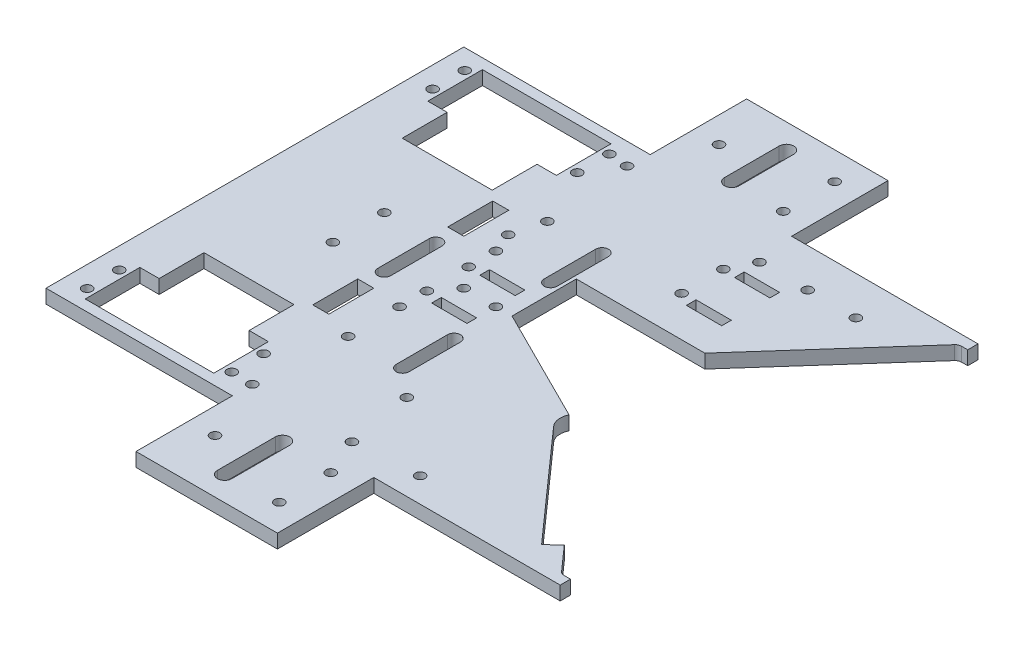
SolidWorks part; units mm, degrees
material "Acrylic (Medium-high impact)"
ref_plane "Front Plane" through (0, 0, 0) normal (0, 0, 1) x (1, 0, 0)
ref_plane "Top Plane" through (0, 0, 0) normal (0, 1, 0) x (1, 0, 0)
ref_plane "Right Plane" through (0, 0, 0) normal (1, 0, 0) x (0, 0, -1)
sketch "Sketch2" plane through (0, 0, 0) normal (0, 1, 0) x (1, 0, 0)
  line L2 (0, 0) -> (0, 65)
  line L3 (0, 65) -> (58, 65)
  line L4 (160, 0) -> (160, 65)
  line L8 (0, 0) -> (160, 0)
  line L9 (102, 65) -> (160, 65)
  line L11 (102, 65) -> (102, 95)
  line L12 (58, 65) -> (58, 95)
  line L13 (58, 95) -> (102, 95)
  dimension "D1" = 65
  dimension "D2" = 160
  dimension "D3" = 44
  dimension "D4" = 30
extrude "Boss-Extrude1" add sketch "Sketch2" along normal blind 4.3
mirror "Mirror1" about plane through (0, 4.3, 0) normal (0, 0, -1) of bodies 101
sketch "Sketch3" plane through (0, 4.3, 0) normal (0, 1, 0) x (1, 0, 0)
  line L0 (160, 61.8) -> (160, -61.8)
  line L1 (120.0126, 20) -> (157.1565, 61.8)
  line L3 (80.0126, 0) -> (80.0126, 20)
  line L4 (80.0126, 20) -> (120.0126, 20)
  line L12 (160, 65) -> (102, 65)
  line L13 (102, 65) -> (102, 95)
  line L15 (102, 95) -> (58, 95)
  line L16 (58, 65) -> (0, 65)
  line L17 (0, 65) -> (0, -65)
  line L18 (0, -65) -> (58, -65)
  line L20 (58, 95) -> (58, 65)
  line L22 (102, -65) -> (160, -65)
  line L23 (160, -65) -> (160, 65)
  line L36 (58, -65) -> (58, -95)
  line L38 (58, -95) -> (102, -95)
  line L39 (58, -95) -> (102, -95)
  line L40 (102, -95) -> (102, -65)
  line L42 (160, -61.8) -> (157.1556, -61.8)
  line L45 (160, 61.8) -> (157.1565, 61.8)
  line L48 (80.0126, 0) -> (120, -20)
  line L49 (120, -20) -> (157.1556, -61.8)
  line M24 (160, -65) -> (160, 65)
  dimension "D2" = 130
  dimension "D3" = 20
  dimension "D4" = 40
  dimension "D1" = 0
extrude "Cut-Extrude1" cut sketch "Sketch3" against normal blind 4.5 contours L48 L49 L1 L4 L3 M24 region at (132.7054, 4.3, -1.1594)
fillet "Fillet1" radius 2 2 edges at (157.1565, 2.15, -61.8) (157.1556, 2.15, 61.8)
ref_axis "Axis1" through (80, 4.3, 95) along (0, 0, -1)
sketch "Sketch4" plane through (0, 4.3, 0) normal (0, 1, 0) x (1, 0, 0)
  line L0 (80, -95) -> (80, 95)
  line L1 (102, -95) -> (58, -95) construction
  line L2 (102, 95) -> (58, 95) construction
ref_plane "Plane2" through (0, 4.3, 0) normal (0, 1, 0) x (1, 0, 0)
sketch "Sketch6" plane through (0, 4.3, 0) normal (0, 1, 0) x (1, 0, 0)
  line L3 (9, -61.8) -> (49, -61.8)
  line L6 (29, -45.8) -> (29, -44.8)
  line L7 (9, -44.8) -> (15, -44.8)
  line L11 (43, -44.8) -> (43, -30.8418)
  line L12 (15, -44.8) -> (15, -30.8418)
  line L13 (15, -30.8418) -> (43, -30.8418)
  line L15 (0, 0) -> (80.0126, 0)
  line L16 (80.0126, 0) -> (120, -20) construction
  line L18 (9, 44.8) -> (15, 44.8)
  line L20 (15, 30.8418) -> (43, 30.8418)
  line L21 (15, 44.8) -> (15, 30.8418)
  line L22 (43, 44.8) -> (43, 30.8418)
  line L25 (15, -45.8) -> (15, -30.8418) construction
  line L27 (9, 61.8) -> (49, 61.8)
  line L30 (4, -61.8) -> (3, -61.8)
  line L31 (0, -61.8) -> (160, -61.8) construction
  line L32 (3, -61.8) -> (4, -61.8)
  line L33 (3, -44.8) -> (3, -62.8) construction
  line L34 (3, -62.8) -> (55, -62.8) construction
  line L35 (55, -44.8) -> (55, -62.8) construction
  line L36 (4, -61.8) -> (54, -61.8) construction
  line L37 (0, 61.8) -> (160, 61.8) construction
  line L38 (54, 61.8) -> (55, 61.8)
  line L39 (54, 61.8) -> (55, 61.8)
  line L40 (43, 44.8) -> (49, 44.8)
  line L41 (4, -45.8) -> (4, -61.8) construction
  line L42 (4, -45.8) -> (54, -45.8) construction
  line L43 (43, -44.8) -> (49, -44.8)
  line L44 (3, -44.8) -> (55, -44.8) construction
  line L45 (29, -45.8) -> (29, -30.8418) construction
  line L46 (43, -45.8) -> (43, -30.8418) construction
  line L47 (54, -45.8) -> (54, -61.8) construction
  line L48 (9, -61.8) -> (49, -61.8)
  line L52 (9, 61.8) -> (9, 44.8)
  line L53 (55, 61.8) -> (54, 61.8)
  line L56 (49, 61.8) -> (49, 44.8)
  line L59 (3, -61.8) -> (4, -61.8)
  line L60 (9, -44.8) -> (9, -61.8)
  line L64 (49, -44.8) -> (49, -61.8)
  dimension "D4" = 1
  dimension "D5" = 14
  dimension "D6" = 14
extrude "Cut-Extrude2" cut sketch "Sketch6" against normal blind 10
sketch "Sketch8" plane through (0, 4.3, 0) normal (0, 1, 0) x (1, 0, 0)
  circle A0 centre (6.5, 58.8) radius 1.5
  circle A1 centre (6.5, 48.8) radius 1.5
  circle A2 centre (51.5, 48.8) radius 1.5
  circle A3 centre (51.5, 58.8) radius 1.5
  circle A4 centre (6.5, -48.7) radius 1.5
  circle A5 centre (6.5, -58.7) radius 1.5
  circle A6 centre (51.5, -58.7) radius 1.5
  circle A7 centre (51.5, -48.8) radius 1.5
  point P23 (0, 0)
  dimension "D7" = 3
extrude "Cut-Extrude3" cut sketch "Sketch8" against normal blind 10
sketch "Sketch9" plane through (0, 0, 0) normal (0, -1, 0) x (1, 0, 0)
  line L0 (75.75, 69.4) -> (75.75, 87.4)
  line L1 (75.75, -87.4) -> (75.75, -70.4)
  line L2 (80.25, -87.4) -> (80.25, -70.4)
  line L4 (80.25, 69.4) -> (80.25, 87.4)
  circle A0 centre (94, 70.4) radius 1.5
  circle A1 centre (66, 78.4) radius 1.5
  circle A2 centre (66, -78.4) radius 1.5
  circle A3 centre (94, -86.4) radius 1.5
  circle A4 centre (94, 86.4) radius 1.5
  circle A5 centre (94, -70.4) radius 1.5
  arc A6 (75.75, -87.4) -> (80.25, -87.4) centre (78, -87.4) ccw
  arc A7 (80.25, -70.4) -> (75.75, -70.4) centre (78, -70.4) ccw
  arc A10 (75.75, 69.4) -> (80.25, 69.4) centre (78, 69.4) ccw
  arc A12 (80.25, 87.4) -> (75.75, 87.4) centre (78, 87.4) ccw
  dimension "D1" = 3
extrude "Cut-Extrude4" cut sketch "Sketch9" against normal blind 10
sketch "Sketch7" plane through (0, 4.3, 0) normal (0, 1, 0) x (1, 0, 0)
  line L0 (0, 0) -> (80.0126, 0)
  line L1 (0, 65) -> (0, -65) construction
  line L2 (80.0126, 0) -> (80.0126, 20) construction
  line L3 (80, -95) -> (80, 95) construction
  line L4 (64, -9) -> (75, -9)
  line L5 (64, -6) -> (75, -6)
  line L6 (64, -9) -> (64, -6)
  line L7 (75, -9) -> (75, -6)
  line L8 (64, -7.5) -> (75, -7.5)
  line L9 (64, 7.5) -> (75, 7.5)
  line L10 (75, 9) -> (75, 6)
  line L11 (64, 9) -> (64, 6)
  line L12 (64, 6) -> (75, 6)
  line L13 (64, 9) -> (75, 9)
  line L14 (104.2547, 30) -> (115.2547, 30)
  line L15 (104.2547, 33) -> (115.2547, 33)
  line L16 (104.2547, 30) -> (104.2547, 33)
  line L17 (115.2547, 30) -> (115.2547, 33)
  line L20 (115.2547, 48) -> (115.2547, 45)
  line L21 (104.2547, 48) -> (104.2547, 45)
  line L22 (104.2547, 45) -> (115.2547, 45)
  line L23 (104.2547, 48) -> (115.2547, 48)
  line L24 (80.0126, 20) -> (120.0126, 20) construction
  circle A0 centre (60.0126, -6.5) radius 1.5
  circle A1 centre (60.0126, 6.5) radius 1.5
  circle A2 centre (100.2673, 32.5) radius 1.5
  circle A3 centre (100.2673, 45.5) radius 1.5
  dimension "D1" = 3
  dimension "D8" = 3
  dimension "D2" = 6.5
  dimension "D3" = 20
  dimension "D6" = 11
  dimension "D4" = 5
  dimension "D5" = 3
  dimension "D7" = 7.5
  dimension "D9" = 11
  dimension "D10" = 3
  dimension "D11" = 12
  dimension "D12" = 13
  dimension "D13" = 10
  dimension "D14" = 3.9874
  dimension "D15" = 0.5
  dimension "D16" = 0.5
  dimension "D17" = 3.9874
sketch "Sketch10" plane through (0, 4.3, 0) normal (0, 1, 0) x (1, 0, 0)
  line L0 (120, -20) -> (156.5589, -61.1287) construction
  line L1 (123.3218, -23.737) -> (149.8964, -53.6334)
  line L2 (116.263, -23.3218) -> (146.1593, -56.9552)
  line L3 (149.8964, -53.6334) -> (146.1593, -56.9552)
  line L4 (120, -20) -> (156.5589, -61.1287) construction
  line L5 (116.263, -23.3218) -> (152.8218, -64.4505) construction
  arc A0 (123.3218, -23.737) -> (116.263, -23.3218) centre (120, -20) ccw
  dimension "D1" = 5
  dimension "D2" = 45
extrude "Cut-Extrude5" cut sketch "Sketch10" against normal blind 10
sketch "Sketch11" plane through (0, 0, 0) normal (0, -1, 0) x (1, 0, 0)
  line L0 (0, 0) -> (80.0126, 0) construction
  line L1 (80, 95) -> (80, -95) construction
  line L2 (80.0126, 0) -> (0, 0)
  line L4 (75, 31.0313) -> (75, 15.0313)
  line L6 (79, 31.0313) -> (79, 15.0313)
  line L7 (79, -31.0313) -> (79, -15.0313)
  line L8 (75, -31.0313) -> (75, -15.0313)
  circle A0 centre (60, 31) radius 1.5
  circle A1 centre (60, 15) radius 1.5
  arc A2 (75, 31.0313) -> (79, 31.0313) centre (77, 31.0313) cw
  arc A3 (75, 15.0313) -> (79, 15.0313) centre (77, 15.0313) ccw
  arc A4 (75, -15.0313) -> (79, -15.0313) centre (77, -15.0313) cw
  arc A5 (75, -31.0313) -> (79, -31.0313) centre (77, -31.0313) ccw
  circle A6 centre (60, -15) radius 1.5
  circle A7 centre (60, -31) radius 1.5
  dimension "D1" = 3
  dimension "D2" = 16
  dimension "D3" = 15
  dimension "D4" = 20
  dimension "D5" = 15
  dimension "D6" = 4
extrude "Cut-Extrude6" cut sketch "Sketch11" against normal blind 10 contours L4 A3 L6 A2 | L8 A5 L7 A4 | A7 | A0 | A1 | A6 region at (77, 0, 23.0313) region at (77, 0, -23.0313) region at (60, 0, -31)
sketch "Sketch12" plane through (0, 0, 0) normal (0, -1, 0) x (-1, 0, 0)
  line L0 (0, 0) -> (-80.0126, 0) construction
  line L3 (-50.2627, -8) -> (-50.2627, 8)
  line L4 (-50.2627, 0) -> (-46.2627, 0)
  line L5 (-46.2627, -8) -> (-46.2627, 8)
  line L6 (0, 0) -> (-46.2627, 0)
  line L7 (0, 65) -> (0, -65) construction
  line L8 (-160, -61.8) -> (0, -61.8) construction
  line L9 (-80.0126, 0) -> (-50.2627, 0)
  line L10 (-80.0126, 0) -> (-115.5281, -17.7634) construction
  line L11 (-80.0126, 0) -> (-80.0126, 20) construction
  line L12 (-58, -65) -> (0, -65) construction
  line L13 (-58, 65) -> (0, 65) construction
  circle A0 centre (-32.2627, -8) radius 1.5
  circle A1 centre (-32.2627, 8) radius 1.5
  arc A2 (-46.2627, 8) -> (-50.2627, 8) centre (-48.2627, 8) ccw
  arc A3 (-50.2627, -8) -> (-46.2627, -8) centre (-48.2627, -8) ccw
  circle A5 centre (-32.2627, -8) radius 1.5 construction
  circle A6 centre (-32.2627, 8) radius 1.5 construction
  dimension "D1" = 3
  dimension "D8" = 8
  dimension "D9" = 8
  dimension "D2" = 8
  dimension "D3" = 14
  dimension "D4" = 4
  dimension "D5" = 61.8
  dimension "D6" = 65
  dimension "D7" = 65
extrude "Cut-Extrude7" cut sketch "Sketch12" against normal blind 10 contours A3 L5 L4 L3 | L4 L5 A2 L3 | A0 | A1 region at (48.2627, 0, 4.7958) region at (48.2627, 0, -4.7958) region at (32.2627, 0, 8) region at (32.2627, 0, -8)
extrude "Cut-Extrude8" cut sketch "Sketch7" against normal blind 9 contours A0 | L4 L7 L5 L6 | L12 L10 L13 L11 | A1 | L23 L20 L22 L21 | L15 L17 L14 L16 | A3 | A2
sketch "Sketch13" plane through (0, 4.3, 0) normal (0, 1, 0) x (1, 0, 0)
  line L0 (80.0126, 0) -> (59.0194, 0)
  line L1 (80, -95) -> (80, 95) construction
  circle A0 centre (65, 0) radius 1.5
  circle A1 centre (75, 0) radius 1.5
  dimension "D2" = 3
  dimension "D3" = 5
  dimension "D1" = 10
extrude "Cut-Extrude9" cut sketch "Sketch13" against normal blind 10 contours L0 A0 | L0 A0 | L0 A1 | L0 A1 region at (75, 4.3, 0.6366) region at (75, 4.3, -0.6366) region at (65, 4.3, 0.6366) region at (65, 4.3, -0.6366)
sketch "Sketch14" plane through (0, 4.3, 0) normal (0, 1, 0) x (1, 0, 0)
  circle A0 centre (57.5, 58.3) radius 1.5
  circle A2 centre (57.5, 21.3) radius 1.5
  circle A3 centre (85.5653, -38.3098) radius 1.5
  circle A4 centre (108.7541, -57.3434) radius 1.5
  dimension "D1" = 3
  dimension "D2" = 3
extrude "Cut-Extrude10" cut sketch "Sketch14" against normal blind 10
sketch "Sketch15" plane through (0, 4.3, 0) normal (0, 1, 0) x (1, 0, 0)
  line L1 (46, 28) -> (51, 28)
  line L2 (46, 28) -> (46, 14)
  line L3 (46, 14) -> (51, 14)
  line L4 (51, 28) -> (51, 14)
  line L6 (0, 65) -> (0, -65) construction
  line L7 (80.0126, 0) -> (53.7017, 0)
  line L8 (46, -14) -> (51, -14)
  line L9 (51, -28) -> (51, -14)
  line L10 (46, -28) -> (51, -28)
  line L11 (46, -28) -> (46, -14)
  arc A0 (50.2627, 8) -> (46.2627, 8) centre (48.2627, 8) ccw construction
  arc A1 (46.2627, -8) -> (50.2627, -8) centre (48.2627, -8) ccw construction
  dimension "D1" = 46
  dimension "D2" = 5
  dimension "D3" = 14
  dimension "D4" = 14
  dimension "D5" = 14
  dimension "D6" = 6
  dimension "D7" = 6
extrude "Cut-Extrude11" cut sketch "Sketch15" against normal blind 10 contours L4 L1 L2 L3 | L11 L10 L9 L8 region at (48.5, 4.3, -21) region at (48.5, 4.3, 21)
sketch "Sketch16" plane through (0, 4.3, 0) normal (0, 1, 0) x (1, 0, 0)
  circle A0 centre (89, -58.8) radius 1.5
  circle A1 centre (58, -58.8) radius 1.5
  dimension "D1" = 3
extrude "Cut-Extrude12" cut sketch "Sketch16" against normal blind 10
ref_plane "Plane3" through (44.2426, 0, 0) normal (1, 0, 0) x (0, 0, -1)
sketch "Sketch17" plane through (44.2426, 0, 0) normal (1, 0, 0) x (0, 0, -1)
  line L4 (0, 0) -> (20, 0)
  line L5 (20, 0) -> (20, 4.3)
  line L6 (20, 4.3) -> (0, 4.3)
  line L7 (0, 4.3) -> (0, 0)
  line L8 (0, 0) -> (20, 0)
  line L9 (20, 0) -> (20, 4.3)
  line L10 (20, 4.3) -> (0, 4.3)
  line L11 (0, 4.3) -> (0, 0)
  circle A0 centre (-2.83, 16.28) radius 0.5
  point P6 (0, 2.15)
  dimension "D4" = 1
  dimension "D2" = 2.83
  dimension "D3" = 14.13
  dimension "D1" = 0
sketch "Sketch18" plane through (0, 4.3, 0) normal (0, 1, 0) x (1, 0, 0)
  line L2 (102, 65) -> (102, 95) construction
  line L3 (160, 65) -> (102, 65) construction
  circle A0 centre (104, 53) radius 1.5
  circle A1 centre (119, 53) radius 1.5
  circle A2 centre (134, 53) radius 1.5
  point P8 (0, 0)
  point P9 (0, 0)
  dimension "D1" = 3
  dimension "D2" = 15
  dimension "D3" = 15
  dimension "D4" = 2
  dimension "D5" = 12
extrude "Cut-Extrude13" cut sketch "Sketch18" against normal blind 10
